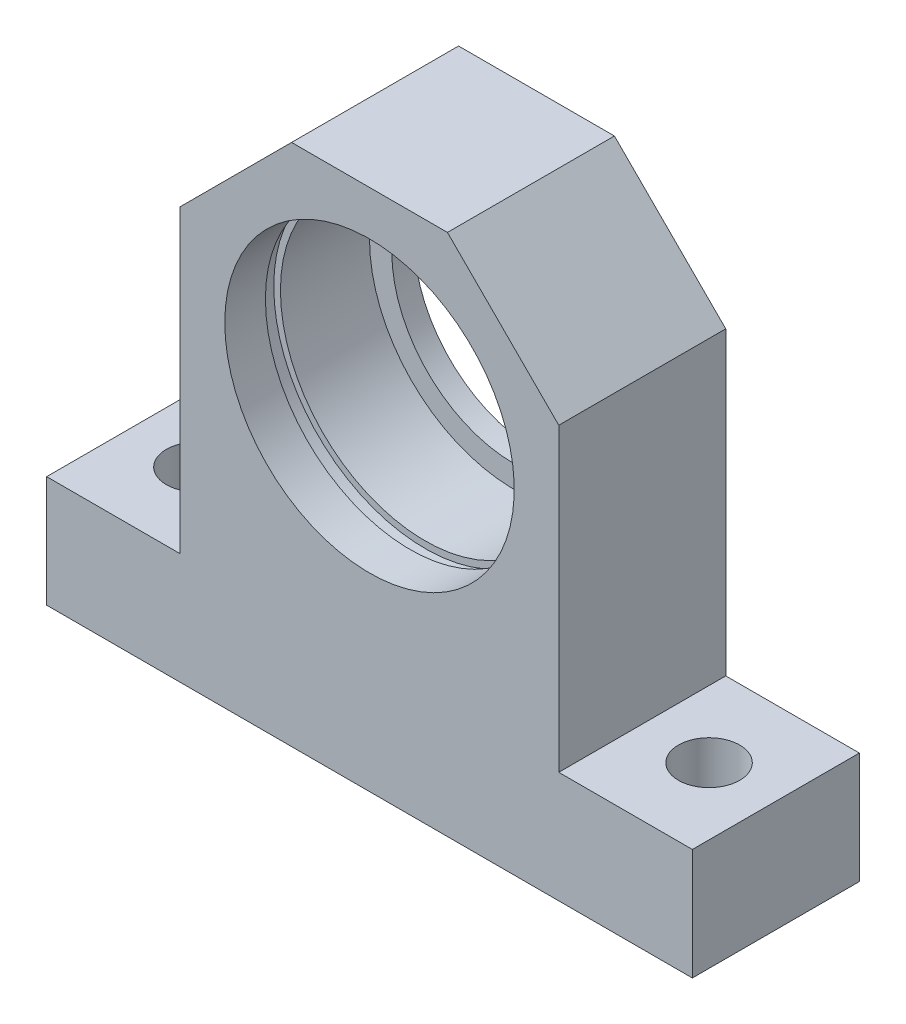
SolidWorks part; units mm, degrees
ref_plane "Front Plane" through (0, 0, 0) normal (0, 0, 1) x (1, 0, 0)
ref_plane "Top Plane" through (0, 0, 0) normal (0, 1, 0) x (1, 0, 0)
ref_plane "Right Plane" through (0, 0, 0) normal (1, 0, 0) x (0, 0, -1)
sketch "Sketch1" plane through (0, 0, 0) normal (0, 0, 1) x (1, 0, 0)
  line L0 (-17, 47) -> (17, 47)
  line L1 (17, 47) -> (17, 10)
  line L2 (17, 10) -> (29, 10)
  line L3 (29, 10) -> (29, 0)
  line L4 (29, 0) -> (-29, 0)
  line L5 (-29, 0) -> (-29, 10)
  line L6 (-29, 10) -> (-17, 10)
  line L7 (-17, 10) -> (-17, 47)
  line L8 (0, 47) -> (0, 0) construction
  point P12 (0, 30)
  dimension "L" = 58
  dimension "S" = 10
  dimension "L2" = 34
  dimension "H_s" = 30
  dimension "H" = 47
  dimension "MSM_6" = 17
extrude "Boss-Extrude1" add sketch "Sketch1" against normal blind 15
sketch "Sketch2" plane through (0, 0, 0) normal (1, 0, 0) x (0, 0, -1)
  line L0 (15, 30) -> (0, 30) construction
  line L1 (3.65, 43) -> (3.65, 43.6)
  line L2 (13, 43) -> (5, 43)
  line L3 (13, 43) -> (13, 41)
  line L4 (13, 41) -> (15, 41)
  line L5 (3.65, 43.6) -> (5, 43.6)
  line L6 (5, 43.6) -> (5, 43)
  line L7 (0, 43) -> (0, 30)
  line L8 (0, 30) -> (15, 30)
  line L9 (15, 30) -> (15, 41)
  line L11 (0, 10) -> (0, 47) construction
  line L12 (3.65, 43) -> (0, 43)
  line L13 (0, 10) -> (0, 47) construction
  line L14 (15, 10) -> (15, 47) construction
  dimension "D" = 26
  dimension "DH_s" = 22
  dimension "B" = 8
  dimension "H_s" = 30
  dimension "L1_s" = 2
  dimension "MSM_2" = 1.35
  dimension "MSM_1" = 27.2
revolve "Cut-Revolve1" cut sketch "Sketch2" angle 360 about L0
hole_wizard "Diameter Hole1" positions "Sketch4" profile "Sketch3" hole size "Ø5.5" standard "JIS" end condition through all
sketch "Sketch4" plane through (0, 10, 0) normal (0, 1, 0) x (1, 0, 0)
  line L10 (0, 0) -> (0, 15) construction
  line L11 (17, 15) -> (-17, 15) construction
  line L12 (-29, 7.5) -> (29, 7.5) construction
  line L13 (-29, 15) -> (-29, 0) construction
  line L14 (29, 15) -> (29, 0) construction
  point P0 (-23, 7.5)
  point P6 (23, 7.5)
  dimension "L1" = 46
  dimension "T/2" = 7.5
sketch "Sketch3" plane through (-23, 10, -7.5) normal (1, 0, 0) x (0, 0, 1)
  line L0 (0, 0) -> (0, 10)
  line L1 (0, 10) -> (2.75, 10)
  line L2 (2.75, 10) -> (2.75, 0)
  line L5 (2.75, 0) -> (0, 0)
  line L11 (0, 0) -> (0, 10) construction
  dimension "D1_s" = 5.5
  dimension "Thru Hole Depth" = 10
chamfer "Chamfer1" distance 10 angle 45 2 edges at (-17, 47, -7.5) (17, 47, -7.5)
chamfer "Chamfer2" [suppressed] distance 2 angle 45
